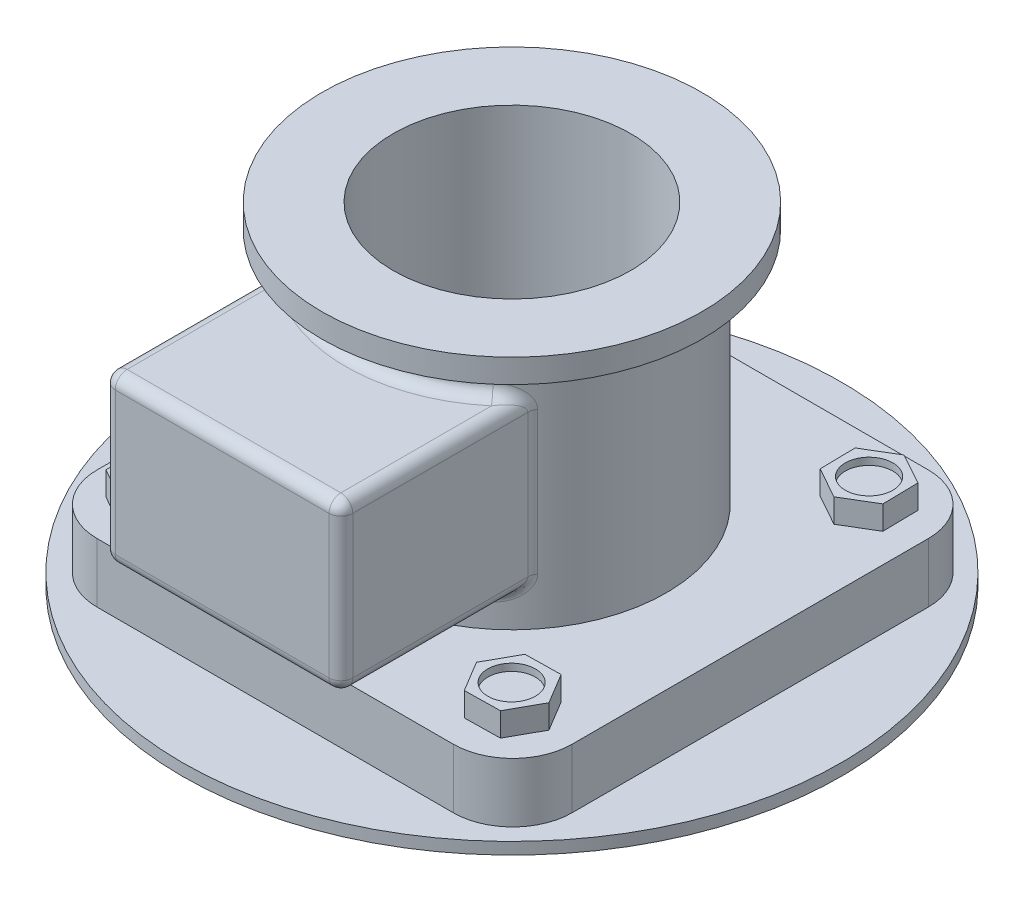
SolidWorks part; units mm, degrees
material "Stainless Steel (ferritic)"
ref_plane "Front Plane" through (0, 0, 0) normal (0, 0, 1) x (1, 0, 0)
ref_plane "Top Plane" through (0, 0, 0) normal (0, 1, 0) x (1, 0, 0)
ref_plane "Right Plane" through (0, 0, 0) normal (1, 0, 0) x (0, 0, -1)
sketch "Sketch1" plane through (0, 0, 0) normal (0, 1, 0) x (1, 0, 0)
  circle A0 centre (0, 0) radius 277.5
extrude "Boss-Extrude1" add sketch "Sketch1" along normal blind 10
sketch "Sketch2" plane through (0, 10, 0) normal (0, 1, 0) x (1, 0, 0)
  line L1 (-199.3488, 200) -> (200.6512, 200)
  line L2 (-199.3488, 200) -> (-199.3488, -200)
  line L3 (-199.3488, -200) -> (200.6512, -200)
  line L4 (200.6512, 200) -> (200.6512, -200)
  line L5 (-199.3488, 200) -> (200.6512, -200) construction
  line L6 (-199.3488, -200) -> (200.6512, 200) construction
  point P0 (4.4291, 3.7779)
  dimension "D1" = 400
  dimension "D2" = 400
  dimension "D3" = 400
extrude "Boss-Extrude2" add sketch "Sketch2" along normal blind 50
fillet "Fillet1" radius 50 4 edges at (-199.3488, 35, -200) (200.6512, 35, -200) (200.6512, 35, 200) (-199.3488, 35, 200)
sketch "Sketch3" plane through (0, 60, 0) normal (0, 1, 0) x (1, 0, 0)
  circle A0 centre (0, 0) radius 130
extrude "Boss-Extrude3" add sketch "Sketch3" along normal blind 200
sketch "Sketch4" plane through (0, 260, 0) normal (0, 1, 0) x (1, 0, 0)
  circle A0 centre (0, 0) radius 160
extrude "Boss-Extrude4" add sketch "Sketch4" along normal blind 20
sketch "Sketch5" plane through (0, 0, 0) normal (0, 0, 1) x (1, 0, 0)
  line L1 (0, -55.0331) -> (0, 375.0331) construction
  line L2 (-149.3488, 60) -> (150.6512, 60) construction
  line L3 (-100, 230) -> (100, 230)
  line L4 (-100, 230) -> (-100, 90)
  line L5 (-100, 90) -> (100, 90)
  line L6 (100, 230) -> (100, 90)
  line L7 (-100, 230) -> (100, 90) construction
  line L8 (-100, 90) -> (100, 230) construction
  point P3 (0, 160)
  dimension "D1" = 140
  dimension "D2" = 200
  dimension "D3" = 30
extrude "Boss-Extrude5" add sketch "Sketch5" along normal blind 244
sketch "Sketch6" plane through (0, 280, 0) normal (0, 1, 0) x (1, 0, 0)
  circle A0 centre (0, 0) radius 100
extrude "Cut-Extrude1" cut sketch "Sketch6" against normal blind 200
fillet "Fillet2" radius 10 12 edges at (0, 90, 130) (0, 230, 130) (-100, 90, 163.5331) (-100, 160, 83.0662) (-100, 230, 163.5331) (0, 90, 244) (-100, 160, 244) (0, 230, 244) (100, 160, 244) (100, 230, 163.5331) (100, 160, 83.0662) (100, 90, 163.5331)
sketch "Sketch7" plane through (0, 60, 0) normal (0, 1, 0) x (1, 0, 0)
  line L0 (-149.3488, -200) -> (150.6512, -200) construction
  line L1 (166.0861, -175.7248) -> (180.647, -149.4954)
  line L2 (180.647, -149.4954) -> (165.2121, -123.7706)
  line L3 (165.2121, -123.7706) -> (135.2164, -124.2752)
  line L4 (135.2164, -124.2752) -> (120.6555, -150.5046)
  line L5 (120.6555, -150.5046) -> (136.0903, -176.2294)
  line L6 (136.0903, -176.2294) -> (166.0861, -175.7248)
  line L7 (200.6512, -150) -> (200.6512, 150) construction
  circle A0 centre (150.6512, -150) radius 25.9808 construction
  dimension "D1" = 30
  dimension "D2" = 50
  dimension "D3" = 50
extrude "Boss-Extrude6" add sketch "Sketch7" along normal blind 20
sketch "Sketch8" plane through (0, 80, 0) normal (0, 1, 0) x (1, 0, 0)
  circle A0 centre (150.2142, -150.5046) radius 20
extrude "Cut-Extrude2" cut sketch "Sketch8" against normal blind 6
pattern_circular "CirPattern1" count 4 over 360 about axis through (0, 260, 0) along (0, -1, 0) of "Boss-Extrude6", "Cut-Extrude2"
